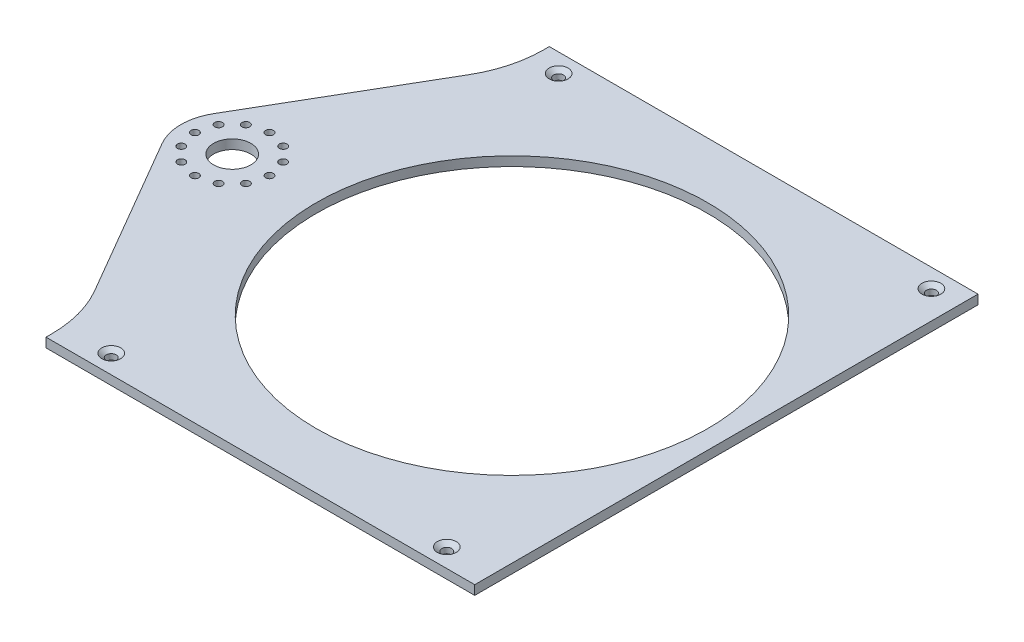
SolidWorks part; units mm, degrees
material "6061-T6 (SS)"
ref_plane "Front Plane" through (0, 0, 0) normal (0, 0, 1) x (1, 0, 0)
ref_plane "Top Plane" through (0, 0, 0) normal (0, 1, 0) x (1, 0, 0)
ref_plane "Right Plane" through (0, 0, 0) normal (1, 0, 0) x (0, 0, -1)
sketch "Sketch1" plane through (0, 0, 0) normal (0, 1, 0) x (1, 0, 0)
  line L0 (0, 0) -> (0, 133.35) construction
  line L1 (0, 133.35) -> (0, 171.45) construction
  line L2 (0, 171.45) -> (146.05, 171.45)
  line L3 (133.35, 0) -> (146.05, 0) construction
  line L4 (146.05, 0) -> (146.05, 171.45)
  line L5 (0, 146.05) -> (74.5442, 146.05) construction
  line L6 (0, 171.45) -> (-146.05, 171.45)
  line L7 (-146.05, 171.45) -> (-146.05, 0) construction
  line L8 (133.35, 0) -> (-146.05, 0) construction
  line L9 (-146.05, 0) -> (-146.05, -171.45) construction
  line L10 (-146.05, -171.45) -> (146.05, -171.45)
  line L11 (146.05, -171.45) -> (146.05, 0)
  line L12 (0, -133.35) -> (0, -171.45) construction
  line L13 (0, 0) -> (-190.6245, 0) construction
  line L14 (-190.6245, 0) -> (-190.6245, 25.4) construction
  line L17 (-220.8112, -17.5646) -> (-146.05, -146.05)
  line L18 (-146.05, -171.45) -> (-146.05, -146.05)
  line L19 (-220.8112, 17.5646) -> (-146.05, 146.05)
  line L20 (-146.05, 146.05) -> (-146.05, 171.45)
  circle A0 centre (0, 0) radius 133.35
  circle A2 centre (-190.6245, 0) radius 12.7
  circle A3 centre (-190.6245, 25.4) radius 2.6289
  circle A4 centre (-177.9245, 21.997) radius 2.6289
  circle A5 centre (-168.6274, 12.7) radius 2.6289
  circle A6 centre (-165.2245, 0) radius 2.6289
  circle A7 centre (-168.6274, -12.7) radius 2.6289
  circle A8 centre (-177.9245, -21.997) radius 2.6289
  circle A9 centre (-190.6245, -25.4) radius 2.6289
  circle A10 centre (-203.3245, -21.997) radius 2.6289
  circle A11 centre (-212.6215, -12.7) radius 2.6289
  circle A12 centre (-216.0245, 0) radius 2.6289
  circle A13 centre (-212.6215, 12.7) radius 2.6289
  circle A14 centre (-203.3245, 21.997) radius 2.6289
  arc A15 (-220.8112, -17.5646) -> (-220.8112, 17.5646) centre (-190.6245, 0) cw
  point P8 (-133.35, 0)
  point P45 (-190.6245, 0)
  dimension "D1" = 266.7
  dimension "D2" = 12.7
  dimension "D8" = 25.4
  dimension "D9" = 5.2578
  dimension "D12" = 34.925
  dimension "D3" = 38.1
  dimension "D4" = 25.4
  dimension "D5" = 12.7
  dimension "D6" = 38.1
  dimension "D7" = 190.6245
  dimension "D10" = 25.4
  dimension "D13" = 25.4
  dimension "D14" = 25.4
  dimension "D11" = 12
extrude "Extrude & center hole" add sketch "Sketch1" along normal blind 6.35
hole_wizard "CSK for 1/4 Flat Head Machine Screw (100)1" positions "Sketch4" profile "Sketch5" countersink size "1/4" standard "ANSI Inch" end condition through all
sketch "Sketch4" plane through (0, 6.35, 0) normal (0, 1, 0) x (1, 0, 0)
  line L0 (-146.05, -171.45) -> (146.05, -171.45) construction
  line L2 (146.05, -171.45) -> (146.05, 171.45) construction
  line L3 (146.05, 171.45) -> (-146.05, 171.45) construction
  line L4 (-146.05, 171.45) -> (-146.05, 146.05) construction
  line L5 (-146.05, -146.05) -> (-146.05, -171.45) construction
  point P0 (-114.3, -158.75)
  point P2 (114.3, -158.75)
  point P4 (127, 158.75)
  point P6 (-127, 158.75)
  dimension "D1" = 12.7
  dimension "D2" = 31.75
  dimension "D3" = 31.75
  dimension "D4" = 12.7
  dimension "D5" = 12.7
  dimension "D6" = 19.05
  dimension "D7" = 12.7
  dimension "D8" = 19.05
sketch "Sketch5" plane through (-114.3, 6.35, 158.75) normal (1, 0, 0) x (0, 0, 1)
  line L0 (0, 0) -> (0, 6.35)
  line L1 (0, 6.35) -> (3.3782, 6.35)
  line L2 (3.3782, 6.35) -> (3.3782, 2.5682)
  line L3 (3.3782, 2.5682) -> (6.4389, 0)
  line L5 (6.4389, 0) -> (0, 0)
  line L6 (-3.3782, 2.5682) -> (-6.4389, 0) construction
  line L11 (0, -6.35) -> (0, 107.95) construction
  dimension "Thru Hole Dia." = 6.7564
  dimension "Thru Hole Depth" = 6.35
  dimension "Near C'Sink Dia." = 12.8778
  dimension "Near C'Sink Angle" = 100
fillet "Fillet1" radius 79.7965 2 edges at (-146.05, 3.175, 146.05) (-146.05, 3.175, -146.05)
